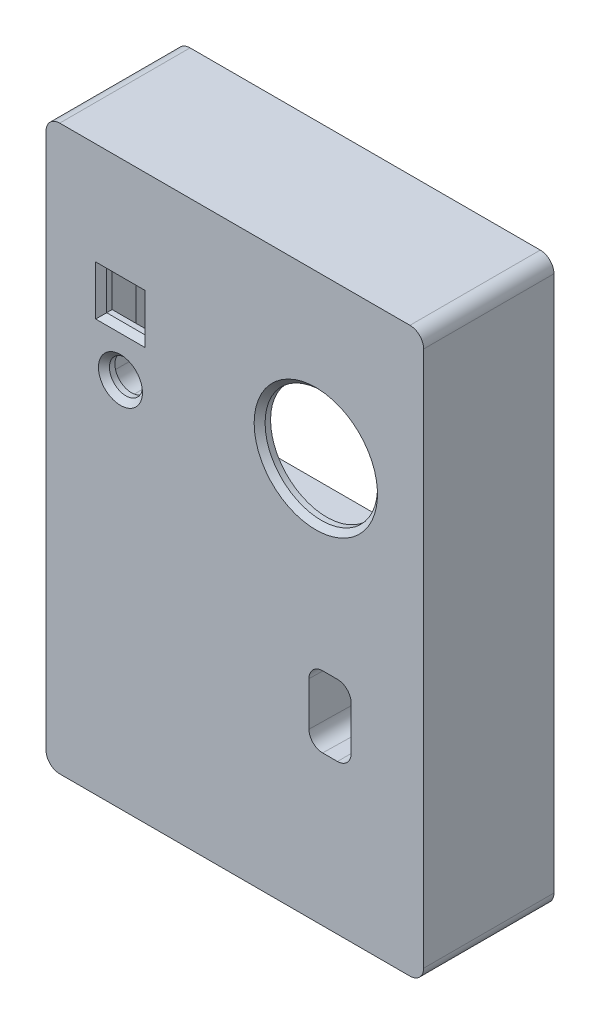
SolidWorks part; units mm, degrees
ref_plane "Front Plane" through (0, 0, 0) normal (0, 0, 1) x (1, 0, 0)
ref_plane "Top Plane" through (0, 0, 0) normal (0, 1, 0) x (1, 0, 0)
ref_plane "Right Plane" through (0, 0, 0) normal (1, 0, 0) x (0, 0, -1)
sketch "Sketch2" plane through (0, 0, 0) normal (0, 0, 1) x (1, 0, 0)
  line L5 (-34.5, -73.3) -> (34.5, -73.3)
  line L6 (-34.5, -73.3) -> (-34.5, 29.7)
  line L7 (-34.5, 29.7) -> (34.5, 29.7)
  line L8 (34.5, -73.3) -> (34.5, 29.7)
extrude "Boss-Extrude1" add sketch "Sketch2" along normal blind 2
sketch "Sketch3" plane through (0, 0, 0) normal (0, 0, -1) x (-1, 0, 0)
  line L1 (34.5, 29.7) -> (-34.5, 29.7)
  line L2 (34.5, 29.7) -> (34.5, -73.3)
  line L3 (34.5, -73.3) -> (-34.5, -73.3)
  line L4 (-34.5, 29.7) -> (-34.5, -73.3)
  line L12 (32.5, -71.3) -> (32.5, 27.7)
  line L13 (32.5, 27.7) -> (-32.5, 27.7)
  line L14 (-32.5, 27.7) -> (-32.5, -71.3)
  line L15 (-32.5, -71.3) -> (32.5, -71.3)
  line L16 (32.5, -71.3) -> (32.5, 27.7)
  line L17 (32.5, 27.7) -> (-32.5, 27.7)
  line L18 (-32.5, 27.7) -> (-32.5, -71.3)
  line L19 (-32.5, -71.3) -> (32.5, -71.3)
  dimension "D1" = 2
extrude "Boss-Extrude2" add sketch "Sketch3" along normal up to surface (21.816 mm away)
sketch "Sketch4" plane through (0, 0, 0) normal (0, 0, -1) x (-1, 0, 0)
  line L0 (24.8, -12.8) -> (16.9635, -12.8) construction
  line L1 (14.4263, -12.8) -> (16.9635, -12.8) construction
  line L2 (14.4263, -12.8) -> (11.7504, -12.8) construction
  line L3 (8.6494, -12.8) -> (11.7504, -12.8) construction
  line L4 (8.6494, -12.8) -> (-2.2511, -12.8) construction
  line L5 (-4.779, -12.8) -> (-2.2511, -12.8) construction
  line L6 (-4.779, -12.8) -> (-12.4624, -12.8) construction
  line L7 (-14.5307, -12.8) -> (-12.4624, -12.8) construction
  line L8 (-14.5307, -12.8) -> (-23.3, -12.8) construction
  line L9 (-27.6, -8.4391) -> (-27.6, -7.6901) construction
  line L10 (-27.6, -6.395) -> (-27.6, -7.6901) construction
  line L11 (-27.6, -6.395) -> (-27.6, -1.8887) construction
  line L12 (-27.6, -0.7629) -> (-27.6, -1.8887) construction
  line L13 (-27.6, -0.7629) -> (-27.6, 3.7404) construction
  line L14 (-27.6, 8.5) -> (-27.6, 3.7404) construction
  line L15 (-23.3, 12.8) -> (-14.5307, 12.8) construction
  line L16 (-12.4624, 12.8) -> (-14.5307, 12.8) construction
  line L17 (-12.4624, 12.8) -> (-4.779, 12.8) construction
  line L18 (-2.2511, 12.8) -> (-4.779, 12.8) construction
  line L19 (-2.2511, 12.8) -> (8.6494, 12.8) construction
  line L20 (11.7504, 12.8) -> (8.6494, 12.8) construction
  line L21 (11.7504, 12.8) -> (14.4263, 12.8) construction
  line L22 (16.9635, 12.8) -> (14.4263, 12.8) construction
  line L23 (16.9635, 12.8) -> (24.8, 12.8) construction
  line L24 (27.6, 10) -> (27.6, 8.6768) construction
  line L25 (27.6, 3.7404) -> (27.6, 8.6768) construction
  line L26 (27.6, 3.7404) -> (27.6, -0.7629) construction
  line L27 (27.6, -1.8887) -> (27.6, -0.7629) construction
  line L28 (27.6, -1.8887) -> (27.6, -6.395) construction
  line L29 (27.6, -7.6901) -> (27.6, -6.395) construction
  line L30 (27.6, -7.6901) -> (27.6, -8.4391) construction
  line L31 (27.6, -10) -> (27.6, -8.4391) construction
  line L32 (24.8, -12.8) -> (16.9635, -12.8) construction
  line L33 (14.4263, -12.8) -> (16.9635, -12.8) construction
  line L34 (14.4263, -12.8) -> (11.7504, -12.8) construction
  line L35 (8.6494, -12.8) -> (11.7504, -12.8) construction
  line L36 (8.6494, -12.8) -> (-2.2511, -12.8) construction
  line L37 (-4.779, -12.8) -> (-2.2511, -12.8) construction
  line L38 (-4.779, -12.8) -> (-12.4624, -12.8) construction
  line L39 (-14.5307, -12.8) -> (-12.4624, -12.8) construction
  line L40 (-14.5307, -12.8) -> (-23.3, -12.8) construction
  line L41 (-27.6, -8.4391) -> (-27.6, -7.6901) construction
  line L42 (-27.6, -6.395) -> (-27.6, -7.6901) construction
  line L43 (-27.6, -6.395) -> (-27.6, -1.8887) construction
  line L44 (-27.6, -0.7629) -> (-27.6, -1.8887) construction
  line L45 (-27.6, -0.7629) -> (-27.6, 3.7404) construction
  line L46 (-27.6, 8.5) -> (-27.6, 3.7404) construction
  line L47 (-23.3, 12.8) -> (-14.5307, 12.8) construction
  line L48 (-12.4624, 12.8) -> (-14.5307, 12.8) construction
  line L49 (-12.4624, 12.8) -> (-4.779, 12.8) construction
  line L50 (-2.2511, 12.8) -> (-4.779, 12.8) construction
  line L51 (-2.2511, 12.8) -> (8.6494, 12.8) construction
  line L52 (11.7504, 12.8) -> (8.6494, 12.8) construction
  line L53 (11.7504, 12.8) -> (14.4263, 12.8) construction
  line L54 (16.9635, 12.8) -> (14.4263, 12.8) construction
  line L55 (16.9635, 12.8) -> (24.8, 12.8) construction
  line L56 (27.6, 10) -> (27.6, 8.6768) construction
  line L57 (27.6, 3.7404) -> (27.6, 8.6768) construction
  line L58 (27.6, 3.7404) -> (27.6, -0.7629) construction
  line L59 (27.6, -1.8887) -> (27.6, -0.7629) construction
  line L60 (27.6, -1.8887) -> (27.6, -6.395) construction
  line L61 (27.6, -7.6901) -> (27.6, -6.395) construction
  line L62 (27.6, -7.6901) -> (27.6, -8.4391) construction
  line L63 (27.6, -10) -> (27.6, -8.4391) construction
  line L64 (-27.6, -8.4391) -> (-27.6, -8.5) construction
  line L65 (-27.6, -8.4391) -> (-27.6, -8.5) construction
  line L66 (24.8, -12.8) -> (16.9635, -12.8)
  line L67 (14.4263, -12.8) -> (16.9635, -12.8)
  line L68 (14.4263, -12.8) -> (11.7504, -12.8)
  line L69 (8.6494, -12.8) -> (11.7504, -12.8)
  line L70 (8.6494, -12.8) -> (-2.2511, -12.8)
  line L71 (-4.779, -12.8) -> (-2.2511, -12.8)
  line L72 (-4.779, -12.8) -> (-12.4624, -12.8)
  line L73 (-14.5307, -12.8) -> (-12.4624, -12.8)
  line L74 (-14.5307, -12.8) -> (-23.3, -12.8)
  line L75 (-27.6, -8.4391) -> (-27.6, -8.5)
  line L76 (-27.6, -8.4391) -> (-27.6, -7.6901)
  line L77 (-27.6, -6.395) -> (-27.6, -7.6901)
  line L78 (-27.6, -6.395) -> (-27.6, -1.8887)
  line L79 (-27.6, -0.7629) -> (-27.6, -1.8887)
  line L80 (-27.6, -0.7629) -> (-27.6, 3.7404)
  line L81 (-27.6, 8.5) -> (-27.6, 3.7404)
  line L82 (-23.3, 12.8) -> (-14.5307, 12.8)
  line L83 (-12.4624, 12.8) -> (-14.5307, 12.8)
  line L84 (-12.4624, 12.8) -> (-4.779, 12.8)
  line L85 (-2.2511, 12.8) -> (-4.779, 12.8)
  line L86 (-2.2511, 12.8) -> (8.6494, 12.8)
  line L87 (11.7504, 12.8) -> (8.6494, 12.8)
  line L88 (11.7504, 12.8) -> (14.4263, 12.8)
  line L89 (16.9635, 12.8) -> (14.4263, 12.8)
  line L90 (16.9635, 12.8) -> (24.8, 12.8)
  line L91 (27.6, 10) -> (27.6, 8.6768)
  line L92 (27.6, 3.7404) -> (27.6, 8.6768)
  line L93 (27.6, 3.7404) -> (27.6, -0.7629)
  line L94 (27.6, -1.8887) -> (27.6, -0.7629)
  line L95 (27.6, -1.8887) -> (27.6, -6.395)
  line L96 (27.6, -7.6901) -> (27.6, -6.395)
  line L97 (27.6, -7.6901) -> (27.6, -8.4391)
  line L98 (27.6, -10) -> (27.6, -8.4391)
  line L99 (29.1, -10) -> (29.1, -8.4391)
  line L100 (29.1, -7.6901) -> (29.1, -8.4391)
  line L101 (29.1, -7.6901) -> (29.1, -6.395)
  line L102 (29.1, -1.8887) -> (29.1, -6.395)
  line L103 (29.1, -1.8887) -> (29.1, -0.7629)
  line L104 (29.1, 3.7404) -> (29.1, -0.7629)
  line L105 (29.1, 3.7404) -> (29.1, 8.6768)
  line L106 (29.1, 10) -> (29.1, 8.6768)
  line L107 (16.9635, 14.3) -> (24.8, 14.3)
  line L108 (16.9635, 14.3) -> (14.4263, 14.3)
  line L109 (11.7504, 14.3) -> (14.4263, 14.3)
  line L110 (11.7504, 14.3) -> (8.6494, 14.3)
  line L111 (-2.2511, 14.3) -> (8.6494, 14.3)
  line L112 (-2.2511, 14.3) -> (-4.779, 14.3)
  line L113 (-12.4624, 14.3) -> (-4.779, 14.3)
  line L114 (-12.4624, 14.3) -> (-14.5307, 14.3)
  line L115 (-23.3, 14.3) -> (-14.5307, 14.3)
  line L116 (-29.1, 8.5) -> (-29.1, 3.7404)
  line L117 (-29.1, -0.7629) -> (-29.1, 3.7404)
  line L118 (-29.1, -0.7629) -> (-29.1, -1.8887)
  line L119 (-29.1, -6.395) -> (-29.1, -1.8887)
  line L120 (-29.1, -6.395) -> (-29.1, -7.6901)
  line L121 (-29.1, -8.4391) -> (-29.1, -7.6901)
  line L122 (-29.1, -8.4391) -> (-29.1, -8.5)
  line L123 (-14.5307, -14.3) -> (-23.3, -14.3)
  line L124 (-14.5307, -14.3) -> (-12.4624, -14.3)
  line L125 (-4.779, -14.3) -> (-12.4624, -14.3)
  line L126 (-4.779, -14.3) -> (-2.2511, -14.3)
  line L127 (8.6494, -14.3) -> (-2.2511, -14.3)
  line L128 (8.6494, -14.3) -> (11.7504, -14.3)
  line L129 (14.4263, -14.3) -> (11.7504, -14.3)
  line L130 (14.4263, -14.3) -> (16.9635, -14.3)
  line L131 (24.8, -14.3) -> (16.9635, -14.3)
  arc A0 (-27.2255, -10.2551) -> (-23.3, -12.8) centre (-23.3, -8.5) ccw construction
  arc A1 (-27.6, -8.5) -> (-27.2255, -10.2551) centre (-23.3, -8.5) ccw construction
  arc A2 (-23.3, 12.8) -> (-27.5958, 8.69) centre (-23.3, 8.5) ccw construction
  arc A3 (27.6, 10) -> (24.8, 12.8) centre (24.8, 10) ccw construction
  arc A4 (24.8, -12.8) -> (27.5961, -10.1486) centre (24.8, -10) ccw construction
  arc A5 (-27.2255, -10.2551) -> (-23.3, -12.8) centre (-23.3, -8.5) ccw construction
  arc A6 (-27.6, -8.5) -> (-27.2255, -10.2551) centre (-23.3, -8.5) ccw construction
  arc A7 (-23.3, 12.8) -> (-27.5958, 8.69) centre (-23.3, 8.5) ccw construction
  arc A8 (27.6, 10) -> (24.8, 12.8) centre (24.8, 10) ccw construction
  arc A9 (24.8, -12.8) -> (27.5961, -10.1486) centre (24.8, -10) ccw construction
  arc A10 (27.5961, -10.1486) -> (27.6, -10) centre (24.8, -10) ccw construction
  arc A11 (27.5961, -10.1486) -> (27.6, -10) centre (24.8, -10) ccw construction
  arc A12 (-27.5958, 8.69) -> (-27.6, 8.5) centre (-23.3, 8.5) ccw construction
  arc A13 (-27.5958, 8.69) -> (-27.6, 8.5) centre (-23.3, 8.5) ccw construction
  arc A14 (-27.2255, -10.2551) -> (-23.3, -12.8) centre (-23.3, -8.5) ccw
  arc A15 (-27.6, -8.5) -> (-27.2255, -10.2551) centre (-23.3, -8.5) ccw
  arc A16 (-27.5958, 8.69) -> (-27.6, 8.5) centre (-23.3, 8.5) ccw
  arc A17 (-23.3, 12.8) -> (-27.5958, 8.69) centre (-23.3, 8.5) ccw
  arc A18 (27.6, 10) -> (24.8, 12.8) centre (24.8, 10) ccw
  arc A19 (27.5961, -10.1486) -> (27.6, -10) centre (24.8, -10) ccw
  arc A20 (24.8, -12.8) -> (27.5961, -10.1486) centre (24.8, -10) ccw
  arc A21 (29.1, 10) -> (24.8, 14.3) centre (24.8, 10) ccw
  arc A22 (-23.3, 14.3) -> (-29.0943, 8.7563) centre (-23.3, 8.5) ccw
  arc A23 (-29.0943, 8.7563) -> (-29.1, 8.5) centre (-23.3, 8.5) ccw
  arc A24 (-29.1, -8.5) -> (-28.5949, -10.8674) centre (-23.3, -8.5) ccw
  arc A25 (-28.5949, -10.8674) -> (-23.3, -14.3) centre (-23.3, -8.5) ccw
  arc A26 (24.8, -14.3) -> (29.0939, -10.2282) centre (24.8, -10) ccw
  arc A27 (29.0939, -10.2282) -> (29.1, -10) centre (24.8, -10) ccw
  dimension "D1" = 0
  dimension "D2" = 1.5
extrude "Boss-Extrude3" add sketch "Sketch4" along normal blind 7.5
sketch "Sketch7" plane through (0, 0, 0) normal (0, 0, -1) x (-1, 0, 0)
  line L2 (24.421, 10.021) -> (17.379, 10.021)
  line L3 (24.421, 10.021) -> (24.421, 2.979)
  line L4 (24.421, 2.979) -> (17.379, 2.979)
  line L5 (17.379, 10.021) -> (17.379, 2.979)
  circle A0 centre (-14.8, 0) radius 10.271
  arc A1 (-5.743, -4.8441) -> (-11.6819, 9.7863) centre (-14.8, 0) ccw construction
  circle A2 centre (20.9, -5.4) radius 3.021
  arc A3 (20.9, -8.421) -> (20.9, -2.379) centre (20.9, -5.4) ccw construction
extrude "Cut-Extrude1" cut sketch "Sketch7" against normal through all
sketch "Sketch9" plane through (0, 0, 0) normal (0, 0, -1) x (-1, 0, 0)
  line L0 (-32.5, -71.3) -> (32.5, -71.3) construction
  line L1 (-24.6, -71.3) -> (-21.1, -71.3)
  line L2 (-24.6, -71.3) -> (-24.6, -61.3)
  line L3 (-24.6, -61.3) -> (-21.1, -61.3)
  line L4 (-21.1, -71.3) -> (-21.1, -61.3)
  line L5 (-22.6, -32.8) -> (-22.6, -67.8) construction
  line L6 (-22.6, -67.8) -> (-22.6, -61.3)
  line L7 (24.4, -69.8) -> (20.9, -69.8)
  line L8 (27.475, -59) -> (10.875, -59) construction
  line L9 (-22.6, -67.8) -> (-21.1, -67.8)
  line L10 (-22.6, -67.8) -> (22.4, -67.8) construction
  line L11 (24.4, -69.8) -> (24.4, -59)
  line L12 (24.4, -59) -> (20.9, -59)
  line L13 (20.9, -69.8) -> (20.9, -59)
  line L16 (22.4, -67.8) -> (22.4, -32.8) construction
  line L17 (20.9, -67.8) -> (22.4, -67.8)
  line L18 (22.4, -67.8) -> (22.4, -59)
  line M17 (-32.5, -71.3) -> (32.5, -71.3)
  dimension "D1" = 2
  dimension "D2" = 3.5
  dimension "D3" = 2
  dimension "D4" = 3.5
  dimension "D5" = 10
  dimension "D6" = 2
extrude "Boss-Extrude4" add sketch "Sketch9" along normal up to surface (19.69 mm away) contours L17 L18 L12 L13 | L9 L4 L3 region at (21.85, -64.55, 0) region at (-21.65, -63.4, 0)
extrude "Boss-Extrude5" add sketch "Sketch9<4>" along normal up to surface (21.3 mm away) contours L18 L17 L13 L11 L12 M17 | L9 L3 L2 L4 M17 region at (23.2361, -66.9757, 0) region at (-23.1866, -64.9366, 0)
sketch "Sketch9<4>" plane through (0, 0, 0) normal (0, 0, -1) x (-1, 0, 0) same geometry as "Sketch9"
sketch "Sketch10" plane through (0, 0, 0) normal (0, 0, -1) x (-1, 0, 0)
  line L1 (22.4, -67.8) -> (22.4, -32.8) construction
  line L2 (10.875, -45.8) -> (27.475, -45.8) construction
  line L3 (22.4, -45.8) -> (24.4, -45.8)
  line L7 (10.625, -33.6125) -> (10.625, -30.8)
  line L9 (21.375, -33.6125) -> (10.625, -33.6125)
  line L10 (10.625, -33.6125) -> (10.625, -37.7125)
  line L11 (10.625, -37.7125) -> (21.375, -37.7125)
  line L12 (21.375, -37.7125) -> (21.375, -33.6125)
  line L16 (22.4, -37.7125) -> (21.375, -37.7125)
  line L18 (22.4, -32.8) -> (-22.6, -32.8) construction
  line L21 (21.375, -33.6125) -> (21.375, -30.8)
  line L22 (21.375, -30.8) -> (24.4, -30.8)
  line L24 (22.4, -45.8) -> (22.4, -37.7125)
  line L25 (22.4, -32.8) -> (22.4, -37.7125)
  line L26 (22.4, -32.8) -> (21.375, -32.8)
  line L27 (24.4, -30.8) -> (24.4, -45.8)
  line L29 (10.625, -30.8) -> (4.6718, -30.8)
  line L30 (4.6718, -30.8) -> (4.6718, -37.7125)
  line L31 (4.6718, -37.7125) -> (10.625, -37.7125)
  line L32 (10.625, -32.8) -> (4.6718, -32.8)
  dimension "D1" = 2
  dimension "D2" = 2
  dimension "D3" = 2
extrude "Boss-Extrude6" add sketch "Sketch10" along normal up to surface (15.33 mm away) contours L11 L12 L9 L10 region at (-16, -35.6625, 0)
extrude "Boss-Extrude7" add sketch "Sketch10<4>" along normal up to surface (19.69 mm away) contours L25 L26 L21 L12 L16 | L7 L32 L30 L31 L10 region at (-21.8875, -35.2563, 0) region at (-7.6484, -35.2563, 0)
sketch "Sketch10<4>" plane through (0, 0, 0) normal (0, 0, -1) x (-1, 0, 0) same geometry as "Sketch10"
extrude "Boss-Extrude8" add sketch "Sketch10<6>" along normal up to surface (21.3 mm away) contours L32 L7 L29 L30 | L27 L22 L21 L26 L25 L24 L3 region at (-23.3033, -37.8842, 0) region at (-7.6484, -31.8, 0)
sketch "Sketch10<6>" plane through (0, 0, 0) normal (0, 0, -1) x (-1, 0, 0) same geometry as "Sketch10"
sketch "Sketch11" plane through (0, 0, 0) normal (0, 0, -1) x (-1, 0, 0)
  line L0 (-16.23, -39.45) -> (-18.77, -39.45) construction
  line L1 (-13.75, -32.95) -> (-21.25, -32.95)
  line L2 (-13.75, -32.95) -> (-13.75, -45.95)
  line L3 (-13.75, -45.95) -> (-21.25, -45.95)
  line L4 (-21.25, -32.95) -> (-21.25, -45.95)
  line L5 (-17.5, -43.61) -> (-17.5, -35.29) construction
  line L6 (-16.23, -38.4) -> (-16.23, -40.5) construction
  line L8 (-18.77, -40.5) -> (-18.77, -38.4) construction
  line L9 (-17.23, -43.61) -> (-17.77, -43.61) construction
  line L10 (-17.77, -35.29) -> (-17.23, -35.29) construction
  point P23 (-17.5, -45.95)
  point P24 (-13.75, -39.45)
  dimension "D1" = 7.5
  dimension "D2" = 13
extrude "Cut-Extrude2" cut sketch "Sketch11" against normal through all
fillet "Fillet2" radius 2.5 4 edges at (34.5, 29.7, -9.908) (34.5, -73.3, -9.908) (-34.5, -73.3, -9.908) (-34.5, 29.7, -9.908)
chamfer "Chamfer1" distance 1 angle 45 6 edges at (-23.921, -5.4, 2) (-20.9, 2.979, 2) (-24.421, 6.5, 2) (-17.379, 6.5, 2) (-20.9, 10.021, 2) (4.529, 0, 2)
sketch "Sketch12" plane through (0, -73.3, 0) normal (0, -1, 0) x (1, 0, 0)
  line L0 (32, -21.816) -> (-32, -21.816) construction
  line L1 (-23.8601, -21.816) -> (-22.8601, -21.816)
  line L2 (-23.8601, -21.816) -> (-23.8601, -9.908)
  line L3 (-23.8601, -9.908) -> (-22.8601, -9.908)
  line L4 (-22.8601, -21.816) -> (-22.8601, -9.908)
  line L5 (-32, 2) -> (-32, -21.816) construction
  line L6 (-12.8601, -21.816) -> (-11.8601, -21.816)
  line L7 (-12.8601, -21.816) -> (-12.8601, -9.908)
  line L8 (-12.8601, -9.908) -> (-11.8601, -9.908)
  line L9 (-11.8601, -21.816) -> (-11.8601, -9.908)
  point P12 (-32, -9.908)
  dimension "D1" = 1
  dimension "D2" = 1
  dimension "D3" = 10
extrude "Cut-Extrude3" cut sketch "Sketch12" against normal up to next
sketch "Sketch13" plane through (0, 0, 0) normal (0, 0, -1) x (-1, 0, 0)
  line L0 (-11.75, -30.95) -> (-11.75, -47.95)
  line L1 (-13.75, -32.95) -> (-21.25, -32.95)
  line L2 (-13.75, -32.95) -> (-13.75, -45.95)
  line L3 (-13.75, -45.95) -> (-21.25, -45.95)
  line L4 (-21.25, -32.95) -> (-21.25, -45.95)
  line L5 (-11.75, -47.95) -> (-23.25, -47.95)
  line L6 (-23.25, -30.95) -> (-23.25, -47.95)
  line L7 (-11.75, -30.95) -> (-23.25, -30.95)
  dimension "D1" = 2
extrude "Boss-Extrude9" add sketch "Sketch13" along normal offset from surface (14.69 mm away) 5
sketch "Sketch14" plane through (0, 0, -14.69) normal (0, 0, -1) x (-1, 0, 0)
  line L0 (-17.22, -34.88) -> (-17.78, -34.88)
  line L1 (-21.25, -32.95) -> (-13.75, -32.95)
  line L2 (-21.25, -32.95) -> (-21.25, -45.95)
  line L3 (-21.25, -45.95) -> (-13.75, -45.95)
  line L4 (-17.22, -34.98) -> (-17.78, -34.98)
  line L5 (-15.92, -42.62) -> (-15.92, -36.28)
  line L6 (-17.78, -43.92) -> (-17.22, -43.92)
  line L7 (-19.08, -36.28) -> (-19.08, -42.62)
  line L8 (-17.22, -34.98) -> (-17.78, -34.98) construction
  line L9 (-15.92, -42.62) -> (-15.92, -36.28) construction
  line L10 (-17.78, -43.92) -> (-17.22, -43.92) construction
  line L11 (-19.08, -36.28) -> (-19.08, -42.62) construction
  line L12 (-13.75, -32.95) -> (-13.75, -45.95)
  line L13 (-19.18, -36.28) -> (-19.18, -42.62)
  line L14 (-17.78, -44.02) -> (-17.22, -44.02)
  line L15 (-15.82, -42.62) -> (-15.82, -36.28)
  arc A0 (-15.82, -36.28) -> (-17.22, -34.88) centre (-17.22, -36.28) ccw
  arc A1 (-17.78, -34.88) -> (-19.18, -36.28) centre (-17.78, -36.28) ccw
  arc A2 (-19.18, -42.62) -> (-17.78, -44.02) centre (-17.78, -42.62) ccw
  arc A3 (-17.22, -44.02) -> (-15.82, -42.62) centre (-17.22, -42.62) ccw
  arc A4 (-17.78, -34.98) -> (-19.08, -36.28) centre (-17.78, -36.28) ccw
  arc A5 (-15.92, -36.28) -> (-17.22, -34.98) centre (-17.22, -36.28) ccw
  arc A6 (-17.22, -43.92) -> (-15.92, -42.62) centre (-17.22, -42.62) ccw
  arc A7 (-19.08, -42.62) -> (-17.78, -43.92) centre (-17.78, -42.62) ccw
  arc A8 (-17.78, -34.98) -> (-19.08, -36.28) centre (-17.78, -36.28) ccw construction
  arc A9 (-15.92, -36.28) -> (-17.22, -34.98) centre (-17.22, -36.28) ccw construction
  arc A10 (-17.22, -43.92) -> (-15.92, -42.62) centre (-17.22, -42.62) ccw construction
  arc A11 (-19.08, -42.62) -> (-17.78, -43.92) centre (-17.78, -42.62) ccw construction
  line M13 (-13.75, -32.95) -> (-13.75, -45.95)
  line M14 (-13.75, -45.95) -> (-21.25, -45.95)
  line M15 (-21.25, -45.95) -> (-21.25, -32.95)
  line M16 (-21.25, -32.95) -> (-13.75, -32.95)
  dimension "D2" = 0.1
  dimension "D1" = 0
extrude "Boss-Extrude10" add sketch "Sketch14" against normal blind 5 contours A11 L11 A8 L8 A9 L9 A10 L10 M13 M16 M15 M14 region at (17.5, -33.1001, -14.69)
draft "Draft1" type of draft neutral plane draft angle 1 faces to draft 1 face at (13.75, -39.45, -3.845) neutral plane through (0, 0, -9.69) neutral plane normal (0, 0, 1) parameters "D1"=1
fillet "Fillet3" radius 2.5 4 edges at (21.25, -45.95, -3.845) (21.25, -32.95, -3.845) (13.648, -32.95, -3.845) (13.648, -45.95, -3.845)
sketch "Sketch15" plane through (0, -71.3, 0) normal (0, 1, 0) x (1, 0, 0)
  line L1 (-20.17, 15.955) -> (-16.17, 15.955)
  line L2 (-20.17, 15.955) -> (-20.17, 19.955)
  line L3 (-20.17, 19.955) -> (-16.17, 19.955)
  line L4 (-16.17, 15.955) -> (-16.17, 19.955)
  arc A0 (-18.17, 18.955) -> (-18.17, 16.955) centre (-18.17, 17.955) ccw construction
  dimension "D1" = 4
  dimension "D2" = 4
  dimension "D3" = 2
  dimension "D4" = 2
extrude "Boss-Extrude11" add sketch "Sketch15" along normal blind 0.6
chamfer "Chamfer3" distance 1 angle 30 1 edges at (-18.17, -71.3, -15.955) first distance on face at (-3.2175, -71.3, -13.3205)
chamfer "Chamfer4" distance 1 angle 30 1 edges at (-18.17, -71.3, -19.955) first distance on face at (-3.2175, -71.3, -13.3205)
sketch "Sketch16" plane through (0, 0, 0) normal (0, 0, -1) x (-1, 0, 0)
  line L0 (24.4, -69.8) -> (24.4, -59) construction
  line L1 (24.4, -67.8) -> (28, -67.8)
  line L2 (24.4, -67.8) -> (24.4, -71.3)
  line L3 (24.4, -71.3) -> (28, -71.3)
  line L4 (28, -67.8) -> (28, -71.3)
  line L5 (23.8601, -71.3) -> (32.5, -71.3) construction
  line L6 (26.75, -71.05) -> (26.75, -67.8)
  line L7 (26.5, 22.2) -> (26.5, -70.8) construction
  line L8 (-24.6, -71.3) -> (-24.6, -61.3) construction
  line L9 (-24.6, -67.8) -> (-28, -67.8)
  line L10 (-24.6, -67.8) -> (-24.6, -71.3)
  line L11 (-24.6, -71.3) -> (-28, -71.3)
  line L12 (-28, -67.8) -> (-28, -71.3)
  line L13 (-32.5, -71.3) -> (11.8601, -71.3) construction
  line L14 (-26.5, -70.8) -> (-26.5, 22.2) construction
  line L15 (-26.75, -71.05) -> (-26.75, -67.8)
  line L16 (-26.75, -67.8) -> (-26.75, -71.05)
  line L17 (-26.75, -71.05) -> (-24.6, -71.05)
  line L18 (26.5, -70.8) -> (-26.5, -70.8) construction
  line L20 (26.75, -71.05) -> (24.4, -71.05)
  line L21 (-26.5, 22.2) -> (26.5, 22.2) construction
  line L22 (28.5, 24.2) -> (24.5, 24.2)
  line L23 (28.5, 24.2) -> (28.5, 20.2)
  line L24 (28.5, 20.2) -> (24.5, 20.2)
  line L25 (24.5, 24.2) -> (24.5, 20.2)
  line L26 (26.75, 20.2) -> (26.75, 22.45)
  line L27 (-24.5, 24.2) -> (-28.5, 24.2)
  line L28 (-24.5, 24.2) -> (-24.5, 20.2)
  line L29 (-24.5, 20.2) -> (-28.5, 20.2)
  line L30 (-28.5, 24.2) -> (-28.5, 20.2)
  line L31 (26.75, 22.45) -> (24.5, 22.45)
  line L32 (-24.5, 22.45) -> (-26.75, 22.45)
  line L33 (-26.75, 22.45) -> (-26.75, 20.2)
  point P27 (-26.5, -70.8)
  point P42 (0, 0)
  line M18 (-21.1, -71.3) -> (32.5, -71.3)
  line M22 (-32.5, -71.3) -> (-24.6, -71.3)
  line M23 (-24.6, -71.3) -> (-24.6, -61.3)
  line M26 (24.4, -59) -> (24.4, -69.8)
  dimension "D1" = 1.5
  dimension "D2" = 1.5
  dimension "D3" = 4
  dimension "D4" = 4
  dimension "D5" = 2
  dimension "D6" = 2
  dimension "D7" = 4
  dimension "D8" = 4
  dimension "D9" = 2
  dimension "D10" = 2
  dimension "D11" = 0.25
  dimension "D12" = 0.25
  dimension "D13" = 0.25
  dimension "D14" = 0.25
  dimension "D15" = 0.25
  dimension "D16" = 0.25
  dimension "D17" = 0.25
  dimension "D18" = 0.25
extrude "Boss-Extrude12" add sketch "Sketch16" along normal up to surface (22.8 mm away) contours L26 L31 L25 L24 | L32 L33 L29 L28 | L15 L17 L10 L9 | L20 L1 L2 M26 region at (-25.575, -69.425, 0) region at (25.675, -69.425, 0) region at (-25.625, 21.325, 0) region at (25.625, 21.325, 0)
extrude "Boss-Extrude13" add sketch "Sketch16<4>" along normal up to surface (23.816 mm away) contours L31 L26 L24 L23 L22 L25 | L33 L32 L28 L27 L30 L29 | L20 L2 L4 L1 M18 | L17 L15 L9 L12 M22 M23 region at (-27.1619, -69.7424, 0) region at (27.189, -69.7278, 0) region at (-26.905, 22.605, 0) region at (26.905, 22.605, 0)
sketch "Sketch16<4>" plane through (0, 0, 0) normal (0, 0, -1) x (-1, 0, 0) same geometry as "Sketch16"
